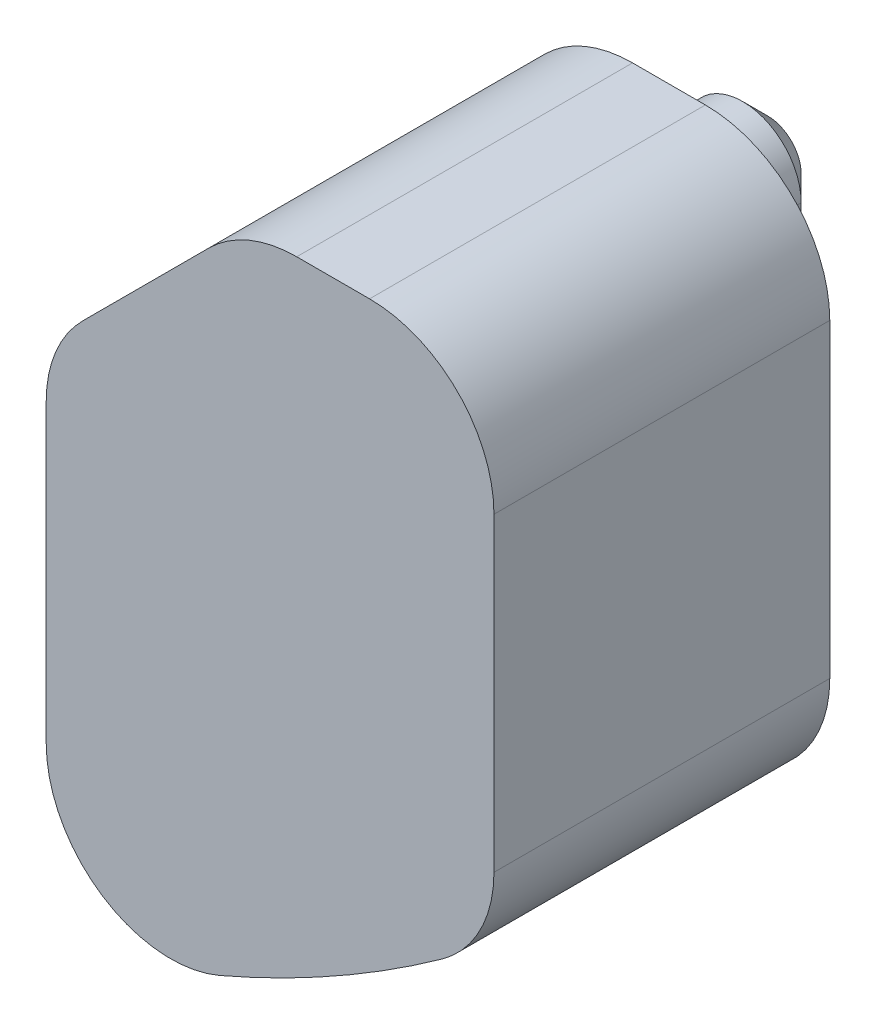
SolidWorks part; units mm, degrees
ref_plane "Front Plane" through (0, 0, 0) normal (0, 0, 1) x (1, 0, 0)
ref_plane "Top Plane" through (0, 0, 0) normal (0, 1, 0) x (1, 0, 0)
ref_plane "Right Plane" through (0, 0, 0) normal (1, 0, 0) x (0, 0, -1)
sketch "Sketch1" plane through (0, 0, 0) normal (0, 0, 1) x (1, 0, 0)
  line L0 (6, -23.2379) -> (6, -12.7602)
  line L1 (6, -12.7602) -> (10, -8.7602)
  line L2 (10, -8.7602) -> (15, -8.7602)
  line L3 (15, -8.7602) -> (15, -18.735)
  line L4 (4, -12.7602) -> (10.3512, -12.7602) construction
  line L5 (3.7103, -12.7602) -> (-1, -12.7602) construction
  line L6 (12, -19) -> (12, -12) construction
  line L8 (4, -20.5602) -> (4, -13.5602) construction
  arc A0 (15, -18.735) -> (6, -23.2379) centre (0, 0) cw
  arc A1 (1.5, -22.7506) -> (10.519, -20.2285) centre (0, 0) ccw construction
  arc A2 (1.5, -23.9531) -> (-1.5, -23.9531) centre (0, 0) ccw construction
  dimension "D2" = 2
  dimension "D1" = 135
  dimension "D3" = 3
  dimension "D4" = 5
extrude "body" add sketch "Sketch1" along normal up to surface (6.75 mm away)
fillet "Fillet1" radius 2.5 5 edges at (6, -12.7602, 3.375) (10, -8.7602, 3.375) (15, -8.7602, 3.375) (15, -18.735, 3.375) (6, -23.2379, 3.375)
hole_wizard "9/64 (0.14063) Diameter Hole1" positions "Sketch2" profile "Sketch3" hole size "9/64" standard "ANSI Inch"
sketch "Sketch2" plane through (6, 0, 0) normal (-1, 0, 0) x (0, 0, 1)
  point P0 (4, -17.0602)
  point P3 (0, 0)
  point P4 (0, 0)
  point P5 (0, 0)
sketch "Sketch3" plane through (6, -17.0602, 4) normal (0, 1, 0) x (0, 0, 1)
  line L0 (0, 0) -> (0, 8.0731)
  line L1 (0, 8.0731) -> (1.786, 7)
  line L2 (1.786, 7) -> (1.786, 1.533)
  line L3 (1.786, 1.533) -> (2.421, 0)
  line L5 (2.421, 0) -> (0, 0)
  line L6 (-1.786, 1.533) -> (-2.421, 0) construction
  line L10 (0, 8.0731) -> (-1.786, 7) construction
  line L11 (0, -6.35) -> (0, 107.95) construction
  dimension "Hole Dia." = 3.572
  dimension "Hole Depth" = 7
  dimension "Near C'Sink Dia." = 4.842
  dimension "Near C'Sink Angle" = 45
  dimension "Drill Angle" = 118
sketch "Sketch4" plane through (0, 0, 0) normal (0, 0, -1) x (-1, 0, 0)
  line L0 (-9.575, -19) -> (-9.575, -12)
  line L1 (-11.925, -19) -> (-11.925, -12)
  line L2 (-12, -12) -> (-12, -19) construction
  arc A0 (-9.575, -19) -> (-11.925, -19) centre (-10.75, -19) cw
  arc A1 (-9.575, -12) -> (-11.925, -12) centre (-10.75, -12) ccw
  arc A2 (-12, -19) -> (-11.922, -19.4347) centre (-10.75, -19) ccw construction
  arc A3 (-9.5, -12) -> (-12, -12) centre (-10.75, -12) ccw construction
  dimension "D1" = 0.075
extrude "mount peg" add sketch "Sketch4" along normal up to surface (3 mm away)
chamfer "peg chamfer" distance 0.5 angle 45 4 edges at (10.75, -20.175, -3) (11.925, -15.5, -3) (10.75, -10.825, -3) (9.575, -15.5, -3)
